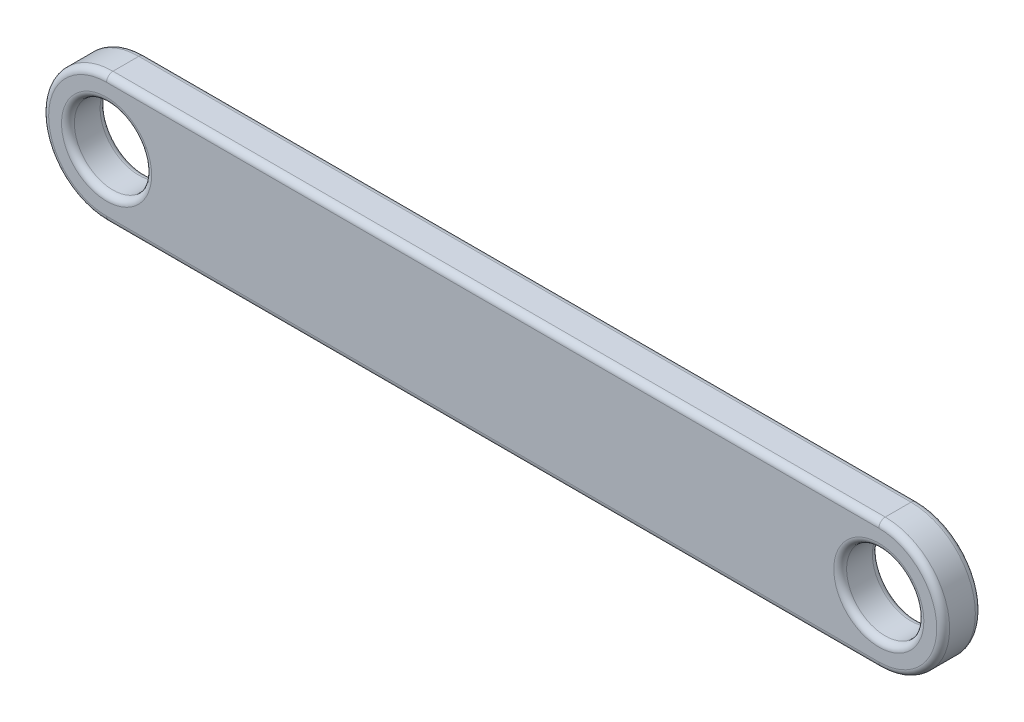
SolidWorks part; units mm, degrees
material "AR-M2"
ref_plane "正面" through (0, 0, 0) normal (0, 0, 1) x (1, 0, 0)
ref_plane "平面" through (0, 0, 0) normal (0, 1, 0) x (1, 0, 0)
ref_plane "右側面" through (0, 0, 0) normal (1, 0, 0) x (0, 0, -1)
sketch "ｽｹｯﾁ1" plane through (0, 0, 0) normal (0, 0, 1) x (1, 0, 0)
  line L0 (0, 0) -> (60, 0) construction
  line L1 (0, 5) -> (60, 5)
  line L2 (60, -5) -> (0, -5)
  arc A0 (0, 5) -> (0, -5) centre (0, 0) ccw
  arc A1 (60, -5) -> (60, 5) centre (60, 0) ccw
  circle A2 centre (0, 0) radius 3
  circle A3 centre (60, 0) radius 3
  dimension "D2" = 10
  dimension "D3" = 10
  dimension "D4" = 6
  dimension "D1" = 60
extrude "ﾎﾞｽ - 押し出し1" add sketch "ｽｹｯﾁ1" along normal blind 3
sketch "ｽｹｯﾁ2" plane through (0, 0, 0) normal (0, 0, -1) x (-1, 0, 0)
  circle A0 centre (0, 0) radius 3
  dimension "D1" = 6
extrude "ｶｯﾄ - 押し出し1" [suppressed] cut sketch "ｽｹｯﾁ2" against normal through all
fillet "ﾌｨﾚｯﾄ1" radius 0.5 12 edges at (63, 0, 0) (30, -5, 0) (65, 0, 0) (30, 5, 0) (-5, 0, 0) (3, 0, 0) (63, 0, 3) (30, 5, 3) (65, 0, 3) (30, -5, 3) (-5, 0, 3) (3, 0, 3)
